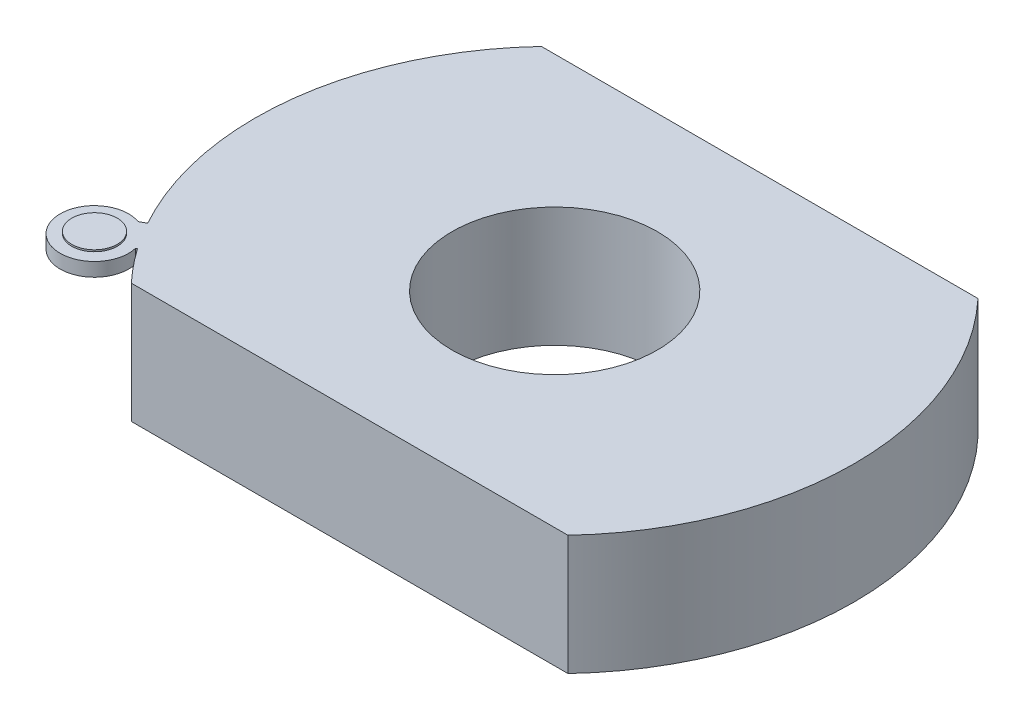
SolidWorks part; units mm, degrees
material "1345 Alloy"
ref_plane "Front Plane" through (0, 0, 0) normal (0, 0, 1) x (1, 0, 0)
ref_plane "Top Plane" through (0, 0, 0) normal (0, 1, 0) x (1, 0, 0)
ref_plane "Right Plane" through (0, 0, 0) normal (1, 0, 0) x (0, 0, -1)
sketch "Sketch1" plane through (0, 0, 0) normal (0, 1, 0) x (1, 0, 0)
  line L0 (-1712.4333, 578.2677) -> (-1658.0172, 559.892) construction
  line L1 (-1682.6566, 611.2885) -> (-1644.8226, 597.5438) construction
  line L2 (-1769.951, 660.0706) -> (-1712.4333, 741.8735) construction
  circle A0 centre (0, 0) radius 1750
  arc A3 (-1712.4333, 578.2677) -> (-1712.4333, 741.8735) centre (-1769.951, 660.0706) cw construction
  arc A4 (-1712.4333, 741.8735) -> (-1682.6566, 611.2885) centre (-1769.951, 660.0706) cw construction
extrude "Boss-Extrude1" add sketch "Sketch1" along normal blind 700
sketch "Sketch9" plane through (0, 0, 0) normal (0, -1, 0) x (1, 0, 0)
  line L1 (-2106.3119, -1198.0599) -> (2106.3119, -1198.0599)
  line L2 (-2106.3119, -1198.0599) -> (-2106.3119, 1198.0599)
  line L3 (-2106.3119, 1198.0599) -> (2106.3119, 1198.0599)
  line L4 (2106.3119, -1198.0599) -> (2106.3119, 1198.0599)
  line L5 (-2106.3119, -1198.0599) -> (2106.3119, 1198.0599) construction
  line L6 (-2106.3119, 1198.0599) -> (2106.3119, -1198.0599) construction
  line L7 (-2636.6179, -2082.9122) -> (2636.6179, -2082.9122)
  line L8 (-2636.6179, -2082.9122) -> (-2636.6179, 2082.9122)
  line L9 (-2636.6179, 2082.9122) -> (2636.6179, 2082.9122)
  line L10 (2636.6179, -2082.9122) -> (2636.6179, 2082.9122)
  line L11 (-2636.6179, -2082.9122) -> (2636.6179, 2082.9122) construction
  line L12 (-2636.6179, 2082.9122) -> (2636.6179, -2082.9122) construction
  point P0 (0, 0)
  point P6 (0, 0)
extrude "Cut-Extrude10" cut sketch "Sketch9" against normal through all both and the other way through all
sketch "Sketch3" plane through (0, 0, 0) normal (0, -1, 0) x (1, 0, 0)
  circle A0 centre (0, 0) radius 600
extrude "Cut-Extrude3" cut sketch "Sketch3" against normal through all both and the other way through all
shell "Shell1" thickness 1.5 removed face at (0, 0, 600)
sketch "Sketch12" plane through (0, 700, 0) normal (0, 1, 0) x (1, 0, 0)
  line L0 (-1432.0962, -1005.7836) -> (-1439.5944, -1011.0497)
  line L1 (-1432.0962, -1005.7836) -> (-1439.5944, -1011.0497)
  line L2 (-1567.0537, -866.7535) -> (-1531.3623, -847.0122)
  line L3 (-1212.6439, -1163.1539) -> (-1531.3623, -847.0122) construction
  line L6 (-1275.5989, 1198.0599) -> (1275.5989, -1198.0599) construction
  line L7 (0, 0) -> (-1750, 0) construction
  line L13 (0, 0) -> (0, 1750) construction
  line L14 (1212.6439, 1163.1539) -> (1394.7434, 1056.9725) construction
  line L15 (1533.0685, 1076.2848) -> (1275.8583, 1198.0599) construction
  line L16 (1432.0962, 1005.7836) -> (1533.0685, 1076.2848)
  line L17 (1432.0962, 1005.7836) -> (1533.0685, 1076.2848)
  line L18 (1456.8867, 1104.0663) -> (1394.7434, 1056.9725)
  arc A0 (-1275.5989, -1198.0599) -> (-1531.3623, -847.0122) centre (0, 0) cw
  arc A1 (-1432.0962, 1005.7836) -> (-1275.5989, 1198.0599) centre (0, 0) ccw construction
  arc A2 (-1439.5944, -1011.0497) -> (-1567.0537, -866.7535) centre (-1634.7144, -1054.9609) cw
  arc A3 (-1432.0962, -1005.7836) -> (-1275.5989, -1198.0599) centre (0, 0) cw construction
  arc A4 (1275.8583, 1198.0599) -> (1394.7434, 1056.9725) centre (24.3381, 22.854) cw
  arc A6 (1533.0685, 1076.2848) -> (1456.8867, 1104.0663) centre (1562.0755, 1274.1701) cw
  arc M6 (-1275.5989, 1198.0599) -> (-1275.5989, -1198.0599) centre (0, 0) ccw
extrude "Boss-Extrude2" add sketch "Sketch12" against normal blind 80 contours A2 L0 L2 M6 region at (-1633.7874, 700, 1053.2699)
sketch "Sketch14" plane through (0, 700, 0) normal (0, 1, 0) x (1, 0, 0)
  circle A0 centre (-1636.0595, -1052.8306) radius 132.8125
extrude "Boss-Extrude5" add sketch "Sketch14" along normal blind 10
sketch "Sketch18" plane through (0, 698.5, 0) normal (0, -1, 0) x (1, 0, 0)
  line L0 (0, 0) -> (-1178.7098, 0) construction
  line L6 (-1278.7098, -100) -> (-1078.7098, -100)
  line L7 (-1278.7098, -100) -> (-1278.7098, 100)
  line L8 (-1278.7098, 100) -> (-1078.7098, 100)
  line L9 (-1078.7098, -100) -> (-1078.7098, 100)
  line L10 (-1278.7098, -100) -> (-1078.7098, 100) construction
  line L11 (-1278.7098, 100) -> (-1078.7098, -100) construction
  circle A0 centre (-1178.7098, 0) radius 27.5
extrude "Boss-Extrude6" add sketch "Sketch18" along normal blind 50
